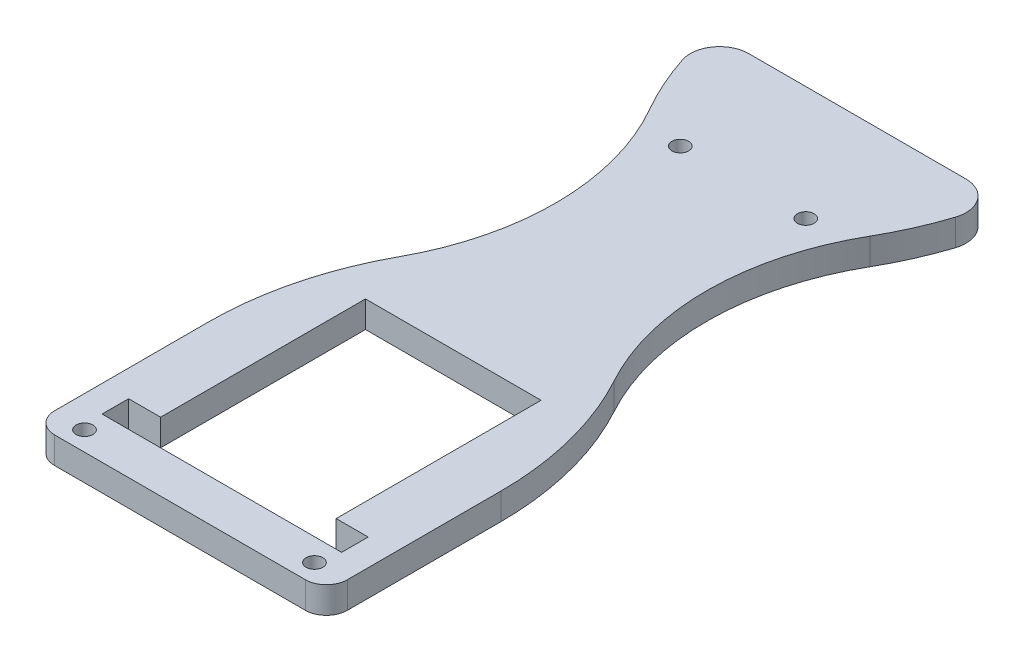
SolidWorks part; units mm, degrees
ref_plane "Front Plane" through (0, 0, 0) normal (0, 0, 1) x (1, 0, 0)
ref_plane "Top Plane" through (0, 0, 0) normal (0, 1, 0) x (1, 0, 0)
ref_plane "Right Plane" through (0, 0, 0) normal (1, 0, 0) x (0, 0, -1)
sketch "Sketch1" plane through (0, 0, 0) normal (0, 1, 0) x (1, 0, 0)
  line L0 (-35, 0) -> (-35, -200)
  line L1 (-35, -200) -> (35, -200)
  line L2 (35, -200) -> (35, 0)
  circle A0 centre (0, 0) radius 35
  point P3 (0, -200)
  dimension "D1" = 70
  dimension "D2" = 70
  dimension "D3" = 200
extrude "Boss-Extrude1" add sketch "Sketch1" along normal mid plane 6.35
sketch "Sketch2" plane through (0, 3.175, 0) normal (0, 1, 0) x (1, 0, 0)
  line L0 (35, -38) -> (-35, -38)
  line L1 (35, -200) -> (35, 0) construction
  line L2 (-35, 0) -> (-35, -200) construction
  line M1 (35, -200) -> (35, 0)
  arc M2 (35, 0) -> (-35, 0) centre (0, 0) ccw
  line M3 (-35, 0) -> (-35, -200)
  dimension "D1" = 38
extrude "Cut-Extrude1" cut sketch "Sketch2" against normal through all contours L0 M1 M2 M3
fillet "Fillet2" [suppressed] radius 8
sketch "Sketch3" plane through (0, 3.175, 0) normal (0, 1, 0) x (1, 0, 0)
  line L0 (-35, -200) -> (35, -200) construction
  line L1 (21, -190) -> (-21, -190)
  line L2 (21, -190) -> (21, -134.65)
  line L3 (21, -134.65) -> (-21, -134.65)
  line L4 (-21, -190) -> (-21, -134.65)
  line L5 (21, -190) -> (-21, -134.65) construction
  line L6 (21, -134.65) -> (-21, -190) construction
  line L8 (-21, -190) -> (-28.65, -190)
  line L9 (-21, -190) -> (-21, -183.65)
  line L10 (-21, -183.65) -> (-28.65, -183.65)
  line L11 (-28.65, -190) -> (-28.65, -183.65)
  line L12 (21, -190) -> (28.65, -190)
  line L13 (21, -190) -> (21, -183.65)
  line L14 (21, -183.65) -> (28.65, -183.65)
  line L15 (28.65, -190) -> (28.65, -183.65)
  point P0 (0, -162.325)
  point P8 (0, -200)
  dimension "D1" = 10
  dimension "D2" = 55.35
  dimension "D3" = 6.35
  dimension "42" = 42
  dimension "D4" = 7.65
extrude "Cut-Extrude2" cut sketch "Sketch3" against normal through all contours L4 L1 L2 L3 | L11 L8 L4 L10 | L12 L15 L14 L2
fillet "Fillet3" radius 5 2 edges at (35, 0, 200) (-35, 0, 200)
sketch "Sketch4" plane through (0, 0, 200) normal (0, 0, 1) x (1, 0, 0)
  line L0 (-30, 3.175) -> (30, 3.175) construction
  arc A0 (-4.7121, 3.175) -> (4.7121, 3.175) centre (0, 4.8471) ccw
  dimension "D1" = 5
extrude "Cut-Extrude3" [suppressed] cut sketch "Sketch4" against normal blind 10 and the other way through all
sketch "Sketch5" plane through (0, 3.175, 0) normal (0, 1, 0) x (1, 0, 0)
  circle A0 centre (27.5, -195.35) radius 2
  circle A1 centre (-27.5, -195.35) radius 2
  circle A2 centre (15, -65.35) radius 2
  circle A3 centre (-15, -65.35) radius 2
extrude "Cut-Extrude4" cut sketch "Sketch5" against normal through all
sketch "Sketch6" plane through (0, 3.175, 0) normal (0, 1, 0) x (1, 0, 0)
  line L1 (-35, -134.65) -> (-35, -49.65)
  line L2 (-35, -38) -> (-35, -195) construction
  arc A0 (-35, -134.65) -> (-35, -49.65) centre (-80, -92.15) ccw
  point P4 (25.6874, -63.5047)
  point P7 (0, 0)
  point P9 (0, 0)
  dimension "D1" = 85
  dimension "D2" = 45
extrude "Cut-Extrude5" cut sketch "Sketch6" against normal through all
mirror "Mirror1" about plane through (0, 0, 0) normal (1, 0, 0) of "Cut-Extrude5"
fillet "Fillet5" radius 76 4 edges at (35, 0, 134.65) (35, 0, 49.65) (-35, 0, 49.65) (-35, 0, 134.65)
fillet "Fillet6" radius 7 2 edges at (35, 0, 38) (-35, 0, 38)
